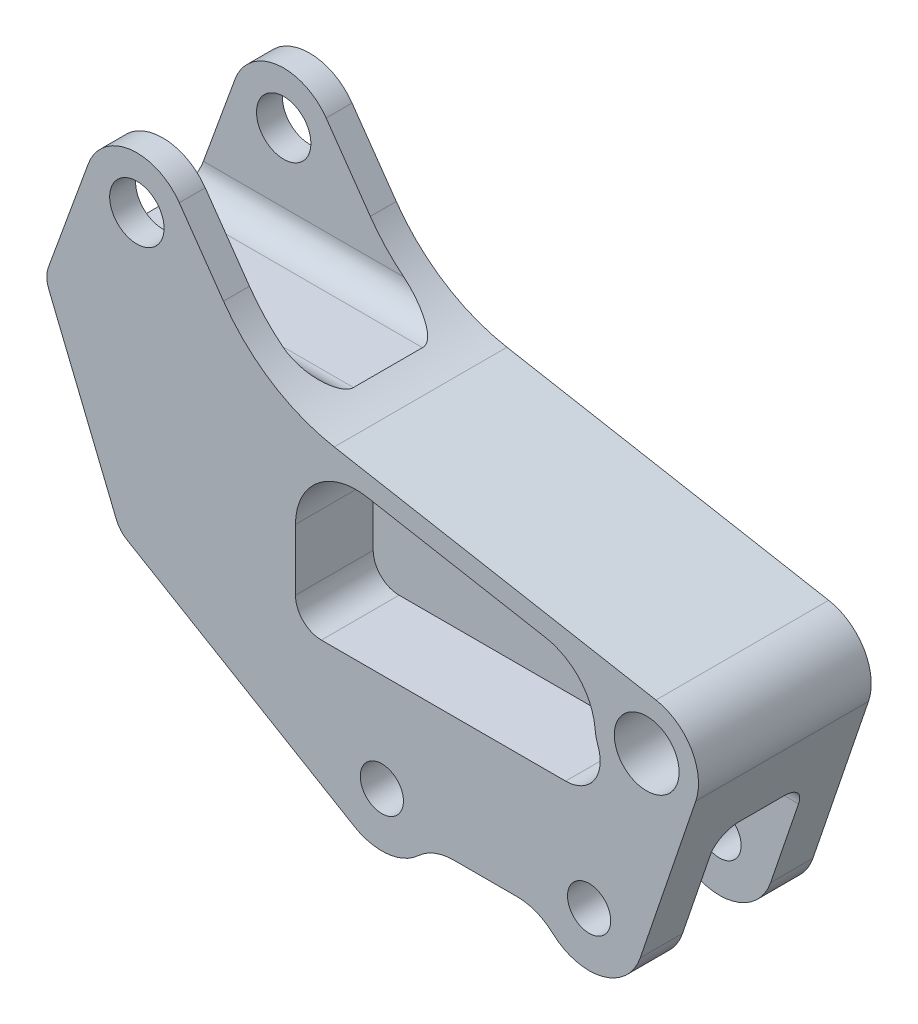
SolidWorks part; units mm, degrees
material "6061-T6 (SS)"
ref_plane "Front Plane" through (0, 0, 0) normal (1, 0, 0) x (0, 1, 0)
ref_plane "Top Plane" through (0, 0, 0) normal (0, 0, 1) x (0, 1, 0)
ref_plane "Right Plane" through (0, 0, 0) normal (0, 1, 0) x (-1, 0, 0)
sketch "Sketch1" plane through (0, 0, 0) normal (0, 0, 1) x (0, 1, 0)
  line L0 (-26.4994, 0.9506) -> (-2.45, -7.2154)
  line L1 (-27.7573, 15.43) -> (-27.7573, 31.9833)
  line L6 (16.5445, 88.4856) -> (34.0097, 82.1288)
  line L7 (-11.2473, 51.6467) -> (-11.2473, -4.2282)
  line L8 (35.7742, 68.7264) -> (26.4934, 62.228)
  line L9 (7.4979, -1.3585) -> (16.0691, 45.9497)
  line L11 (-9.4693, 53.4247) -> (15.6555, 53.4247)
  line L12 (-9.4693, 47.8367) -> (-9.4693, 11.9174)
  line L13 (-5.6593, 51.6467) -> (3.3583, 51.6467)
  line L15 (17.4335, 88.1621) -> (17.4335, 50.7405)
  line L16 (15.6555, 88.1229) -> (15.6555, 53.4247)
  line L17 (7.3396, 14.865) -> (12.1058, 41.1718)
  line L20 (16.5445, 57.1222) -> (6.8134, 3.412) construction
  line L21 (16.5445, 88.4856) -> (16.5445, 57.1222) construction
  line L22 (16.5445, 57.1222) -> (41.0622, 41.4215) construction
  line L32 (-25.6569, 51.6467) -> (-11.2473, 51.6467)
  line L33 (-30.779, 42.988) -> (-10.3583, 77.5084)
  line L34 (-10.3583, 77.5084) -> (16.5445, 88.4856)
  line L38 (-10.3583, -4.5301) -> (-10.3583, 77.5084) construction
  line L39 (-9.4693, 53.4247) -> (-9.4693, 77.8711)
  line L40 (-10.3583, 52.5357) -> (-25.131, 52.5357) construction
  line L41 (-24.6052, 53.4247) -> (-11.2473, 53.4247)
  line L42 (-11.2473, 53.4247) -> (-11.2473, 76.0056)
  line L43 (31.4035, 74.9684) -> (17.4335, 74.9684) construction
  circle A0 centre (0, 0) radius 4.7625
  circle A1 centre (31.4035, 74.9684) radius 4
  circle A2 centre (-23.9473, 38.9467) radius 3.175
  circle A3 centre (-23.9473, 8.4667) radius 3.175
  arc A4 (-2.45, -7.2154) -> (7.4979, -1.3585) centre (0, 0) ccw
  arc A5 (-30.779, 42.988) -> (-27.7573, 31.9833) centre (-23.9473, 38.9467) ccw
  arc A6 (35.7742, 68.7264) -> (34.0097, 82.1288) centre (31.4035, 74.9684) ccw
  arc A7 (-27.7573, 15.43) -> (-26.4994, 0.9506) centre (-23.9473, 8.4667) ccw
  arc A8 (26.4934, 62.228) -> (16.0691, 45.9497) centre (41.0622, 41.4215) ccw
  arc A10 (-9.4693, 47.8367) -> (-5.6593, 51.6467) centre (-5.6593, 47.8367) cw
  arc A13 (3.3583, 51.6467) -> (12.1058, 41.1718) centre (3.3583, 42.7567) cw
  arc A14 (-9.4693, 11.9174) -> (-2.6336, 7.1504) centre (-4.3893, 11.9174) ccw
  arc A15 (-2.6336, 7.1504) -> (-0.6498, 7.5922) centre (0, 0) cw
  arc A16 (-0.6498, 7.5922) -> (7.3396, 14.865) centre (-1.4079, 16.4499) ccw
  point P55 (19.6722, 55.1192)
  dimension "D1" = 9.525
  dimension "D2" = 6.35
  dimension "D3" = 8
  dimension "D4" = 6.35
  dimension "D10" = 1.778
  dimension "D11" = 15.24
  dimension "D12" = 15.875
  dimension "D13" = 15.875
  dimension "D14" = 15.24
  dimension "D18" = 25.4
  dimension "D22" = 3.048
  dimension "D23" = 3.81
  dimension "D29" = 8.89
  dimension "D30" = 5.08
  dimension "D31" = 8.89
  dimension "D39" = 2.54
  dimension "D34" = 12.7
  dimension "D19" = 35
  dimension "D35" = 1.778
  dimension "D5" = 81.28
  dimension "D6" = 45.72
  dimension "D7" = 66.04
  dimension "D8" = 25.4
  dimension "D9" = 30.48
  dimension "D15" = 12.7
  dimension "D16" = 13.97
  dimension "D17" = 12.7
  dimension "D20" = 1.778
  dimension "D21" = 3.81
  dimension "D24" = 20
  dimension "D25" = 3.81
extrude "Boss-Extrude1" add sketch "Sketch1" along normal blind 12.7 contours A8 L15 L8 L7 L0 A4 L9 L16 L11 A16 A15 A14 L12 A10 L13 A13 L17 A0 | A8 L8 L15 | L8 A6 A1 | L1 A7 L0 L7 A5 A2 A3 | L41 L42 L34 L33 | L39 L11 L16 L34 region at (-25.0117, -19.949, 0) region at (-23.7092, -10.1941, 0) region at (-60.9516, -15.7, 0) region at (-72.6999, 25.1629, 0) region at (-68.3589, 3.8189, 0)
extrude "Boss-Extrude2" add sketch "Sketch1<4>" along normal blind 1.27 contours A15 A16 L17 A13 L13 A10 L12 A14 region at (-30.7751, 0.07, 0)
sketch "Sketch1<4>" plane through (0, 0, 0) normal (0, 0, 1) x (0, 1, 0) same geometry as "Sketch1"
extrude "Cut-Extrude1" cut sketch "Sketch1<6>" along normal blind 6.477 contours L1 A7 L0 L7 L32 L33 A5 A2 A3 region at (-25.0117, -19.949, 0)
sketch "Sketch1<6>" plane through (0, 0, 0) normal (0, 0, 1) x (0, 1, 0) same geometry as "Sketch1"
extrude "Cut-Extrude3" cut sketch "Sketch1<10>" along normal blind 8.89 contours A8 L8 A6 L6 L15 A1 | L41 L42 L33 | L39 L11 L16 L34 region at (-60.9516, -15.7, 0) region at (-72.6999, 25.1629, 0) region at (-68.3589, 3.8189, 0)
sketch "Sketch1<10>" plane through (0, 0, 0) normal (0, 0, 1) x (0, 1, 0) same geometry as "Sketch1"
mirror "Mirror1" about plane through (0, 0, 0) normal (0, 0, 1) of bodies 107 103
sketch "Sketch3" plane through (0, 0, 0) normal (0, 0, 1) x (0, 1, 0)
  line L0 (-23.9473, 38.9467) -> (31.4035, 74.9684) construction
  line L1 (-11.2473, 51.6467) -> (-11.2473, -4.2282) construction
  line L2 (-23.9473, 38.9467) -> (-118.6003, -15.7012) construction
  line L3 (31.4035, 74.9684) -> (85.9954, 47.2192) construction
  circle A0 centre (31.4035, 74.9684) radius 4 construction
  circle A1 centre (-23.9473, 38.9467) radius 3.175 construction
  dimension "D1" = 120
  dimension "D2" = 60
fillet "Fillet1" radius 3.81 10 edges at (-69.4513, 17.4335, 8.89) (-51.6467, -18.4521, 6.477) (-51.6467, -18.4521, -6.477) (-53.4247, -17.9263, 8.89) (-53.4247, -17.9263, -8.89) (-70.7738, 15.6555, 8.89) (-65.6479, -9.4693, 8.89) (-65.6479, -9.4693, -8.89) (-70.7738, 15.6555, -8.89) (-69.4513, 17.4335, -8.89)
fillet "Fillet3" radius 3.81 2 edges at (-77.5084, -10.3583, 0) (-88.4856, 16.5445, 0)
fillet "Fillet4" radius 3.175 10 edges at (-21.8042, -11.2473, 6.477) (-21.8042, -11.2473, -6.477) (-50.5307, -11.2473, 5.3611) (-51.6467, -11.2473, 0) (-50.5307, -11.2473, -5.3611) (-53.4247, -11.2473, 0) (-66.6201, -11.2473, 8.89) (-54.5406, -11.2473, 7.7741) (-66.6201, -11.2473, -8.89) (-54.5406, -11.2473, -7.7741)
fillet "Fillet5" radius 7.62 4 edges at (-15.43, -27.7573, 9.5885) (-31.9833, -27.7573, 9.5885) (-15.43, -27.7573, -9.5885) (-31.9833, -27.7573, -9.5885)
